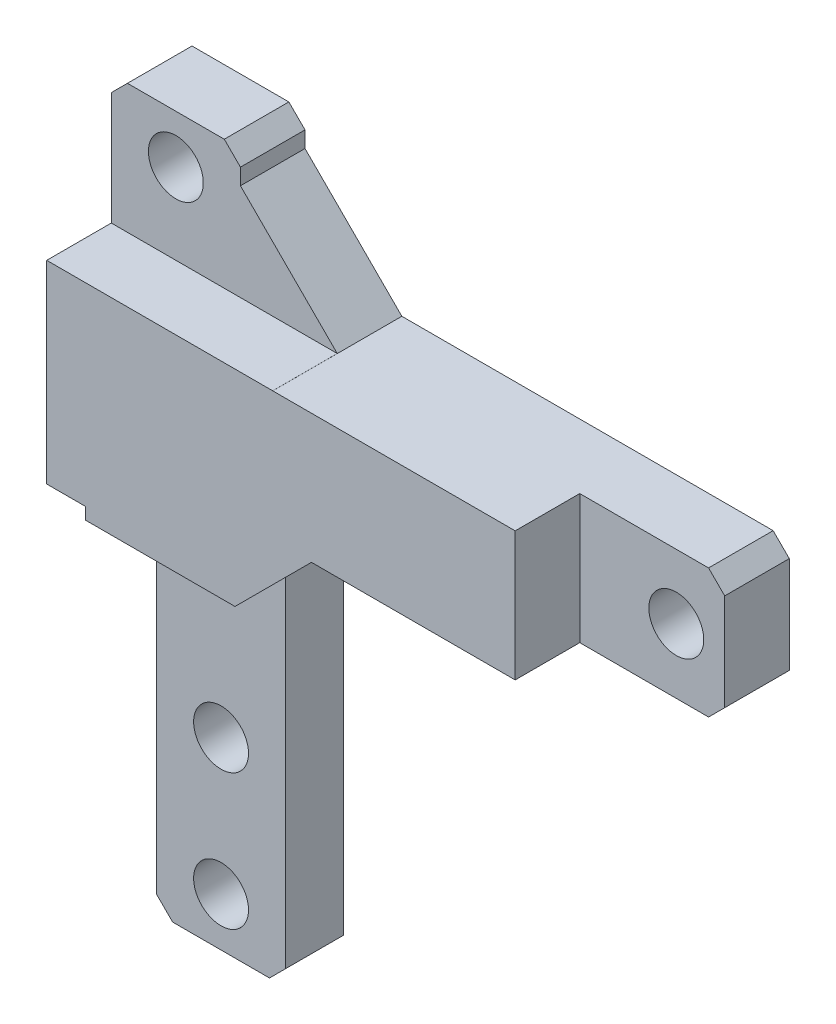
SolidWorks part; units mm, degrees
ref_plane "前视基准面" through (0, 0, 0) normal (0, 0, 1) x (1, 0, 0)
ref_plane "上视基准面" through (0, 0, 0) normal (0, 1, 0) x (1, 0, 0)
ref_plane "右视基准面" through (0, 0, 0) normal (1, 0, 0) x (0, 0, -1)
other "Configuration Table"
sketch "草图1" plane through (0, 0, 0) normal (0, 0, 1) x (1, 0, 0)
  line L0 (-4.3, -2.5) -> (9.5, -2.5)
  line L1 (-5.5, 1.5) -> (9.5, 1.5)
  line L4 (9.5, 1.5) -> (9.5, -2.5)
  line L8 (-9.5, 1.5) -> (-9.5, 5.5)
  line L9 (-9.5, 5.5) -> (-5.5, 5.5)
  line L11 (-5.5, 1.5) -> (-5.5, 5.5)
  line L12 (-9.5, 1.5) -> (-9.5, -4.5)
  line L13 (-8.3, -4.5) -> (-8.3, -16.5)
  line L14 (-8.3, -16.5) -> (-4.3, -16.5)
  line L15 (-4.3, -16.5) -> (-4.3, -2.5)
  line L16 (-9.5, -4.5) -> (-8.3, -4.5)
  circle A0 centre (8, -0.5) radius 0.85
  circle A1 centre (-7.5, 4) radius 0.85
  circle A2 centre (-6.3, -15) radius 0.85
  circle A3 centre (-6.3, -10.8) radius 0.85
  point P0 (0, 0)
  dimension "D16" = 1.7
  dimension "D2" = 6
  dimension "D4" = 2
  dimension "D5" = 1.5
  dimension "D6" = 10
  dimension "D7" = 4
  dimension "D9" = 2
  dimension "D10" = 1.5
  dimension "D11" = 4
  dimension "D12" = 4
  dimension "D13" = 2
  dimension "D14" = 19
  dimension "D17" = 4.2
  dimension "D18" = 1.5
  dimension "D19" = 2
extrude "凸台-拉伸1" add sketch "草图1" along normal blind 4
sketch "草图2" plane through (0, 0, 4) normal (0, 0, 1) x (1, 0, 0)
  line L0 (-8.3, -4.8687) -> (-4.3, -4.8687)
  line L10 (9.5, -2.5) -> (9.5, 1.5)
  line L11 (9.5, 1.5) -> (-5.5, 1.5)
  line L12 (-5.5, 1.5) -> (-5.5, 5.5)
  line L13 (-5.5, 5.5) -> (-9.5, 5.5)
  line L14 (-9.5, 5.5) -> (-9.5, -4.5)
  line L15 (-9.5, -4.5) -> (-8.3, -4.5)
  line L16 (-8.3, -4.5) -> (-8.3, -16.5)
  line L17 (-8.3, -16.5) -> (-4.3, -16.5)
  line L18 (-4.3, -16.5) -> (-4.3, -2.5)
  line L19 (-4.3, -2.5) -> (9.5, -2.5)
  line L26 (-8.3, -4.8687) -> (-8.3, -16.5)
  line L27 (-8.3, -16.5) -> (-4.3, -16.5)
  line L28 (-4.3, -16.5) -> (-4.3, -4.8687)
  circle A0 centre (-6.3, -15) radius 0.85 construction
  circle A1 centre (-6.3, -10.8) radius 0.85 construction
  circle A2 centre (-6.3, -15) radius 0.85
  circle A3 centre (-6.3, -10.8) radius 0.85
  dimension "D1" = 0
extrude "切除-拉伸1" cut sketch "草图2" against normal blind 2.2
sketch "草图3" plane through (0, 0, 4) normal (0, 0, -1) x (-1, 0, 0)
  line L0 (-5.0101, 1.5) -> (-5.0101, -2.5)
  line L1 (5.5, 1.5011) -> (9.5, 1.5011)
  line L10 (-9.5, 1.5) -> (-9.5, -2.5)
  line L11 (-9.5, -2.5) -> (4.3, -2.5)
  line L12 (4.3, -2.5) -> (4.3, -16.5)
  line L13 (4.3, -16.5) -> (8.3, -16.5)
  line L14 (8.3, -16.5) -> (8.3, -4.5)
  line L15 (8.3, -4.5) -> (9.5, -4.5)
  line L16 (9.5, -4.5) -> (9.5, 5.5)
  line L17 (9.5, 5.5) -> (5.5, 5.5)
  line L18 (5.5, 5.5) -> (5.5, 1.5)
  line L19 (5.5, 1.5) -> (-9.5, 1.5)
  line L20 (-9.5, 1.5) -> (-9.5, -2.5)
  line L21 (-9.5, -2.5) -> (-5.0101, -2.5)
  line L26 (9.5, 1.5011) -> (9.5, 5.5)
  line L27 (9.5, 5.5) -> (5.5, 5.5)
  line L28 (5.5, 5.5) -> (5.5, 1.5011)
  line L29 (-5.0101, 1.5) -> (-9.5, 1.5)
  circle A0 centre (-8, -0.5) radius 0.85 construction
  circle A1 centre (7.5, 4) radius 0.85 construction
  circle A2 centre (-8, -0.5) radius 0.85
  circle A3 centre (7.5, 4) radius 0.85
  dimension "D1" = 0
extrude "切除-拉伸2" cut sketch "草图3" along normal blind 2
chamfer "倒角1" distance 3 angle 45 2 edges at (-4.3, -2.5, 2) (-5.5, 1.5, 2)
chamfer "倒角2" distance 0.5 angle 45 6 edges at (-4.3, -16.5, 0.9) (-8.3, -16.5, 0.9) (-9.5, 5.5, 1) (9.5, -2.5, 1) (9.5, 1.5, 1) (-5.5, 5.5, 1)
